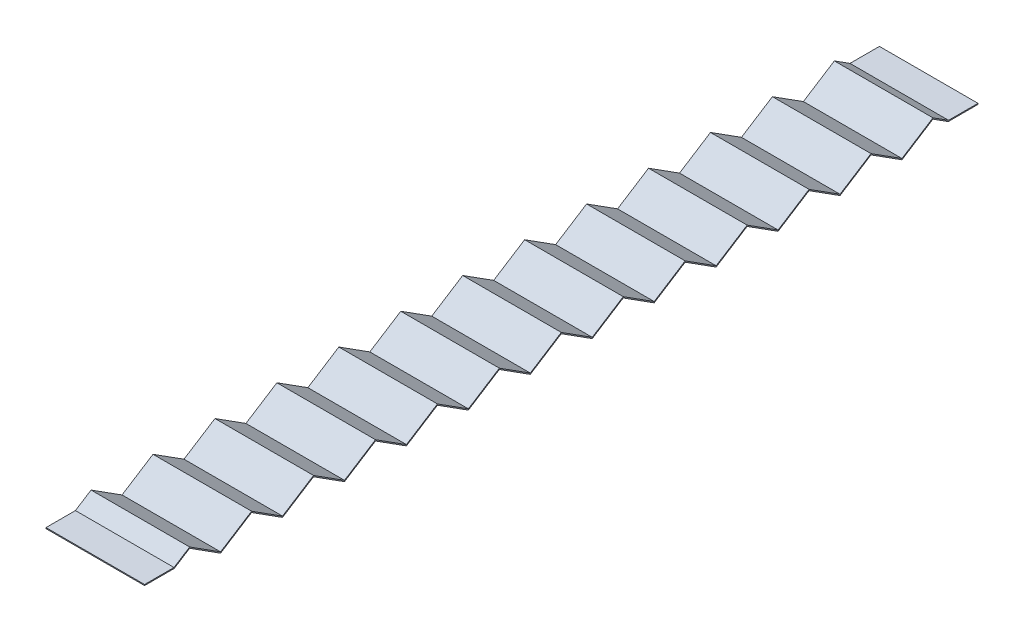
SolidWorks part; units mm, degrees
ref_plane "Front Plane" through (0, 0, 0) normal (0, 0, 1) x (1, 0, 0)
ref_plane "Top Plane" through (0, 0, 0) normal (0, 1, 0) x (1, 0, 0)
ref_plane "Right Plane" through (0, 0, 0) normal (1, 0, 0) x (0, 0, -1)
sketch "Sketch2" plane through (0, 0, 0) normal (0, 0, 1) x (1, 0, 0)
  line L1 (-27.5, 10) -> (27.5, 10)
  line L2 (-27.5, 10) -> (-27.5, 0)
  line L3 (-27.5, 0) -> (27.5, 0)
  line L4 (27.5, 10) -> (27.5, 0)
  point P4 (0, 0)
  dimension "D1" = 10
  dimension "D2" = 55
sketch "Sketch3" plane through (0, 0, 0) normal (1, 0, 0) x (0, 0, -1)
  line L0 (0, 10) -> (422.6978, 10) construction
  line L1 (0, 0) -> (422.6978, 0) construction
  line L3 (15, 5) -> (22.854, 10)
  line L4 (22.854, 10) -> (38.5619, 0)
  line L5 (38.5619, 0) -> (54.2698, 10)
  line L6 (54.2698, 10) -> (69.9777, 0)
  line L7 (69.9777, 0) -> (85.6856, 10)
  line L8 (85.6856, 10) -> (101.3935, 0)
  line L9 (101.3935, 0) -> (117.1014, 10)
  line L10 (117.1014, 10) -> (132.8093, 0)
  line L11 (132.8093, 0) -> (148.5172, 10)
  line L12 (148.5172, 10) -> (164.2252, 0)
  line L13 (164.2252, 0) -> (179.9331, 10)
  line L14 (179.9331, 10) -> (195.641, 0)
  line L15 (195.641, 0) -> (211.3489, 10)
  line L16 (211.3489, 10) -> (227.0568, 0)
  line L17 (227.0568, 0) -> (242.7647, 10)
  line L18 (242.7647, 10) -> (258.4726, 0)
  line L19 (0, 10) -> (0, 0) construction
  line L20 (258.4726, 0) -> (274.1805, 10)
  line L21 (274.1805, 10) -> (289.8884, 0)
  line L22 (289.8884, 0) -> (305.5964, 10)
  line L23 (305.5964, 10) -> (321.3043, 0)
  line L24 (321.3043, 0) -> (337.0122, 10)
  line L25 (337.0122, 10) -> (352.7201, 0)
  line L26 (352.7201, 0) -> (368.428, 10)
  line L27 (368.428, 10) -> (384.1359, 0)
  line L28 (384.1359, 0) -> (399.8438, 10)
  line L29 (399.8438, 10) -> (407.6978, 5)
  line L30 (422.6978, 10) -> (422.6978, 0) construction
  line L31 (15, 5) -> (0, 5)
  line L32 (407.6978, 5) -> (422.6978, 5)
  line L33 (422.6978, -12.3958) -> (422.6978, -19.8536) construction
  dimension "D2" = 15
  dimension "D1" = 10
  dimension "D3" = 15
extrude "Extrude-Thin1" add sketch "Sketch3" against normal mid plane 50 thin thin type mid plane wall 0.5
